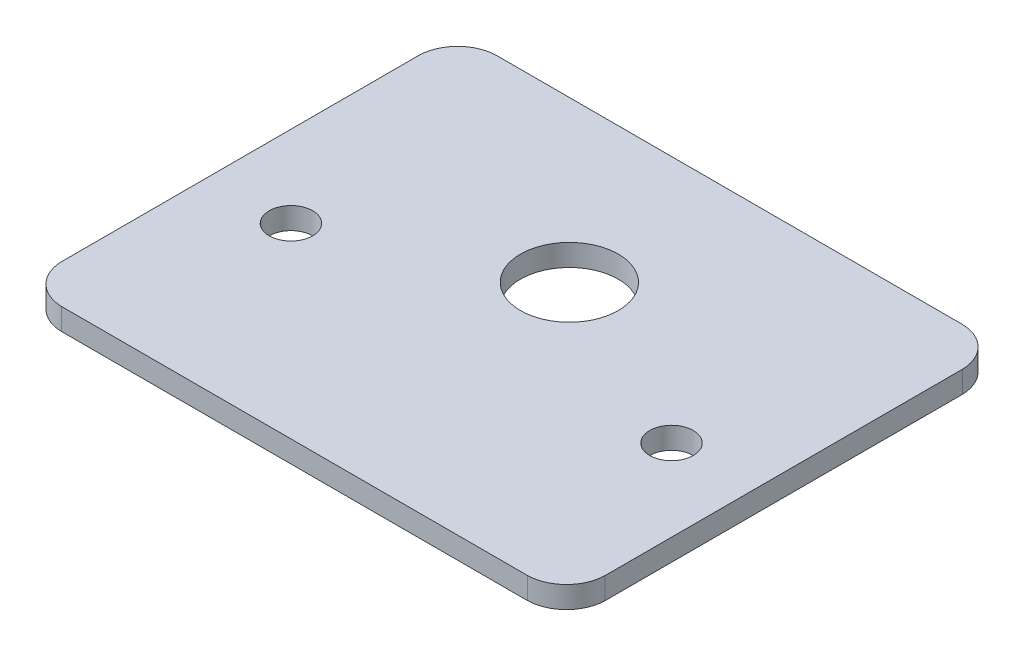
SolidWorks part; units mm, degrees
ref_plane "Front Plane" through (0, 0, 0) normal (0, 0, 1) x (1, 0, 0)
ref_plane "Top Plane" through (0, 0, 0) normal (0, 1, 0) x (1, 0, 0)
ref_plane "Right Plane" through (0, 0, 0) normal (1, 0, 0) x (0, 0, -1)
sketch "Sketch1" plane through (0, 0, 0) normal (0, 1, 0) x (1, 0, 0)
  line L0 (0, -3.7692) -> (0, -12.0494) construction
  line L5 (-25, 20) -> (25, 20)
  line L6 (-25, 20) -> (-25, -20)
  line L7 (-25, -20) -> (25, -20)
  line L8 (25, 20) -> (25, -20)
  line L9 (-25, 20) -> (25, -20) construction
  line L10 (-25, -20) -> (25, 20) construction
  line L11 (-5.3094, 0) -> (-10.9893, 0) construction
  circle A0 centre (0, 5.2766) radius 4.5
  circle A1 centre (-17.5072, -2.826) radius 2
  circle A2 centre (17.4928, -2.826) radius 2
  arc A3 (-25, -16.277) -> (-21.447, -20) centre (-21.362, -16.362) ccw
  arc A4 (-25, 16.277) -> (-21.447, 20) centre (-21.362, 16.362) cw
  arc A5 (25, 16.277) -> (21.447, 20) centre (21.362, 16.362) ccw
  arc A6 (25, -16.277) -> (21.447, -20) centre (21.362, -16.362) cw
  point P0 (0, 0)
  dimension "D1" = 50
  dimension "D2" = 40
extrude "Boss-Extrude2" add sketch "Sketch1" along normal blind 2 contours A6 L8 A5 L5 A4 L6 A3 L7 A2 A1 A0 region at (0.0001, 0, 0.1393)
